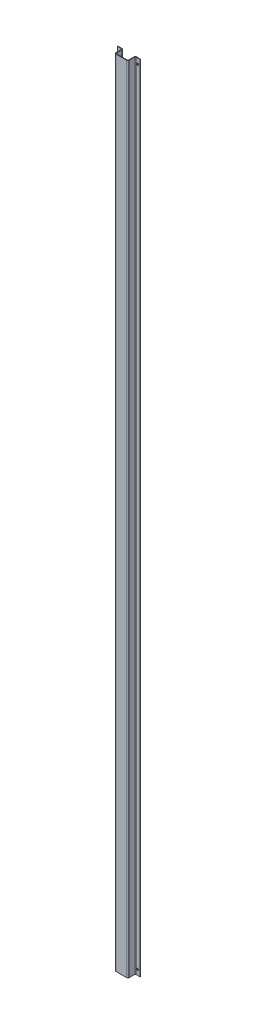
SolidWorks part; units mm, degrees
note: The reader was unsure of these and kept them because the rebuilt part matched: flange length of "Edge-Flange1", "Edge-Flange2".
material "Galvanized Steel"
ref_plane "Front" through (0, 0, 0) normal (0, 0, 1) x (1, 0, 0)
ref_plane "Top" through (0, 0, 0) normal (0, 1, 0) x (1, 0, 0)
ref_plane "Right" through (0, 0, 0) normal (1, 0, 0) x (0, 0, -1)
sketch "Sketch1" plane through (0, 0, 0) normal (0, 0, 1) x (1, 0, 0)
  line L1 (-25, -1500) -> (25, -1500)
  line L2 (-25, -1500) -> (-25, 1500)
  line L3 (-25, 1500) -> (25, 1500)
  line L4 (25, -1500) -> (25, 1500)
  line L5 (-25, -1500) -> (25, 1500) construction
  line L6 (-25, 1500) -> (25, -1500) construction
  point P0 (0, 0)
  dimension "D1" = 50
  dimension "D2" = 3000
base flange "Base-Flange1" sketch "Sketch1" thickness 2 reverse thickness direction no parameters "D1"=13
edge flange "Edge-Flange1" sketch "Sketch10" flange profiles "Sketch10", "Sketch11" flange angle 90 flange length 30 flange position material inside bend radius 2.5 thickness 2 relief rectangular parameters "D6"=10, "D8"=1
sketch "Sketch10" plane through (25, 0, -2) normal (-1, 0, 0) x (0, 1, 0)
  line L2 (-1500, 0) -> (-1500, 28)
  line L3 (-1500, 28) -> (1500, 28)
  line L4 (1500, 28) -> (1500, 0)
  line L5 (1500, 0) -> (-1500, 0) construction
  line L6 (1500, 0) -> (-1500, 0)
sketch "Sketch11" plane through (-25, 0, -2) normal (1, 0, 0) x (0, -1, 0)
  line L2 (-1500, 0) -> (-1500, 28)
  line L3 (-1500, 28) -> (1500, 28)
  line L4 (1500, 28) -> (1500, 0)
  line L5 (1500, 0) -> (-1500, 0) construction
  line L6 (1500, 0) -> (-1500, 0)
bend "EdgeBend1" bend radius 2.5 bend angle 90 parameters "D5"=1
bend "EdgeBend2" bend radius 2.5 bend angle 90 parameters "D5"=2
edge flange "Edge-Flange2" sketch "Sketch16" flange profiles "Sketch16", "Sketch17" flange angle 90 flange length 20 flange position material inside bend radius 2.5 thickness 2 relief rectangular parameters "D6"=10, "D8"=1
sketch "Sketch16" plane through (-25, 0, -30) normal (0, 0, -1) x (0, -1, 0)
  line L0 (1500, 0) -> (-1500, 0) construction
  line L1 (1500, 0) -> (-1500, 0)
  line L2 (-1500, 0) -> (-1500, 18)
  line L3 (-1500, 18) -> (1500, 18)
  line L4 (1500, 18) -> (1500, 0)
sketch "Sketch17" plane through (25, 0, -30) normal (0, 0, -1) x (0, 1, 0)
  line L0 (1500, 0) -> (-1500, 0) construction
  line L1 (1500, 0) -> (-1500, 0)
  line L2 (-1500, 0) -> (-1500, 18)
  line L3 (-1500, 18) -> (1500, 18)
  line L4 (1500, 18) -> (1500, 0)
bend "EdgeBend3" bend radius 2.5 bend angle 90 parameters "D5"=3
bend "EdgeBend4" bend radius 2.5 bend angle 90 parameters "D5"=4
sketch "Sketch18" plane through (0, 0, -28) normal (0, 0, 1) x (1, 0, 0)
  line L0 (-27.5, -1500) -> (-43, -1500) construction
  line L1 (-43, -1500) -> (-43, 1500) construction
  circle A0 centre (-34, -1480) radius 3.5
  dimension "D2" = 7
  dimension "D1" = 20
  dimension "D3" = 9
extrude "Cut-Extrude1" cut sketch "Sketch18" against normal blind 10 normal cut yes
mirror "Mirror1" about plane through (0, 0, 0) normal (0, 1, 0) of "Cut-Extrude1"
mirror "Mirror2" about plane through (0, 0, 0) normal (1, 0, 0) of "Mirror1", "Cut-Extrude1"
sketch "Bend-Lines1" [suppressed] plane through (0, 0, 0) normal (0, 1, 0) x (1, 0, 0)
sketch "Bounding-Box1" [suppressed] plane through (0, 0, 0) normal (0, 1, 0) x (1, 0, 0)
sheet metal parameters "Sheet-Metal1" thickness 2 parameters "D1"=13
flat pattern "Flat-Pattern1" [suppressed]
sketch "Bend-Lines2" plane through (0, 0, 0) normal (0, 1, 0) x (1, 0, 0)
sketch3d "Bounding-Box2" [suppressed]
  line L0 (-20, 1500, 0) -> (-20, -1500, 0) construction
  line L1 (20, 1500, 0) -> (20, -1500, 0) construction
  line L2 (-20, 1500, 0) -> (20, 1500, 0) construction
  line L3 (-20, -1500, 0) -> (20, -1500, 0) construction
sheet metal parameters "Sheet-Metal2" thickness 2 parameters "D1"=13
flat pattern "Flat-Pattern1"
sketch "Bend-Lines2" plane through (0, 0, 0) normal (0, 0, 1) x (1, 0, 0)
  line L0 (-18.2489, 1500) -> (-18.2489, -1500) construction
  line L1 (18.2489, -1500) -> (18.2489, 1500) construction
  line L2 (-18.2489, 1500) -> (-18.2489, -1500) construction
  line L3 (18.2489, -1500) -> (18.2489, 1500) construction
sketch3d "Bounding-Box2" [suppressed]
  line L0 (46.4978, 1500, 0) -> (46.4978, -1500, 0) construction
  line L1 (-46.4978, 1500, 0) -> (-46.4978, -1500, 0) construction
  line L2 (46.4978, 1500, 0) -> (-46.4978, 1500, 0) construction
  line L3 (46.4978, -1500, 0) -> (-46.4978, -1500, 0) construction
bend of the flat pattern "Flatten-<EdgeBend1>1"
bend of the flat pattern "Flatten-<EdgeBend2>1"
sheet metal parameters "Sheet-Metal3" thickness 2 parameters "D1"=13
flat pattern "Flat-Pattern1"
sketch "Bend-Lines2" plane through (0, 0, 0) normal (0, 0, 1) x (1, 0, 0)
  line L0 (-23.2489, 1500) -> (-23.2489, -1500) construction
  line L1 (23.2489, -1500) -> (23.2489, 1500) construction
  line L2 (-23.2489, 1500) -> (-23.2489, -1500) construction
  line L3 (23.2489, -1500) -> (23.2489, 1500) construction
  line L4 (49.7467, -1500) -> (49.7467, 1500) construction
  line L5 (-49.7467, 1500) -> (-49.7467, -1500) construction
  line L6 (49.7467, -1500) -> (49.7467, 1500) construction
  line L7 (-49.7467, 1500) -> (-49.7467, -1500) construction
sketch3d "Bounding-Box2" [suppressed]
  line L0 (67.9956, 1500, 0) -> (67.9956, -1500, 0) construction
  line L1 (-67.9956, 1500, 0) -> (-67.9956, -1500, 0) construction
  line L2 (67.9956, 1500, 0) -> (-67.9956, 1500, 0) construction
  line L3 (67.9956, -1500, 0) -> (-67.9956, -1500, 0) construction
bend of the flat pattern "Flatten-<EdgeBend1>1"
bend of the flat pattern "Flatten-<EdgeBend2>1"
bend of the flat pattern "Flatten-<EdgeBend3>1"
bend of the flat pattern "Flatten-<EdgeBend4>1"
sheet metal parameters "Sheet-Metal4" thickness 2 parameters "D1"=13
flat pattern "Flat-Pattern1"
sketch "Bend-Lines2" plane through (0, 0, 0) normal (0, 0, 1) x (1, 0, 0)
  line L0 (-23.2489, 1500) -> (-23.2489, -1500) construction
  line L1 (23.2489, -1500) -> (23.2489, 1500) construction
  line L2 (-23.2489, 1500) -> (-23.2489, -1500) construction
  line L3 (23.2489, -1500) -> (23.2489, 1500) construction
  line L4 (49.7467, -1500) -> (49.7467, 1500) construction
  line L5 (-49.7467, 1500) -> (-49.7467, -1500) construction
  line L6 (49.7467, -1500) -> (49.7467, 1500) construction
  line L7 (-49.7467, 1500) -> (-49.7467, -1500) construction
sketch3d "Bounding-Box2" [suppressed]
  line L0 (67.9956, 1500, 0) -> (67.9956, -1500, 0) construction
  line L1 (-67.9956, 1500, 0) -> (-67.9956, -1500, 0) construction
  line L2 (67.9956, 1500, 0) -> (-67.9956, 1500, 0) construction
  line L3 (67.9956, -1500, 0) -> (-67.9956, -1500, 0) construction
bend of the flat pattern "Flatten-<EdgeBend1>1"
bend of the flat pattern "Flatten-<EdgeBend2>1"
bend of the flat pattern "Flatten-<EdgeBend3>1"
bend of the flat pattern "Flatten-<EdgeBend4>1"
sheet metal parameters "Sheet-Metal5" thickness 2 parameters "D1"=13
flat pattern "Flat-Pattern1"
sketch "Bend-Lines2" plane through (0, 0, 0) normal (0, 0, 1) x (1, 0, 0)
  line L0 (-23.2489, 1500) -> (-23.2489, -1500) construction
  line L1 (23.2489, -1500) -> (23.2489, 1500) construction
  line L2 (-23.2489, 1500) -> (-23.2489, -1500) construction
  line L3 (23.2489, -1500) -> (23.2489, 1500) construction
  line L4 (49.7467, -1500) -> (49.7467, 1500) construction
  line L5 (-49.7467, 1500) -> (-49.7467, -1500) construction
  line L6 (49.7467, -1500) -> (49.7467, 1500) construction
  line L7 (-49.7467, 1500) -> (-49.7467, -1500) construction
sketch3d "Bounding-Box2" [suppressed]
  line L0 (67.9956, 1500, 0) -> (67.9956, -1500, 0) construction
  line L1 (-67.9956, 1500, 0) -> (-67.9956, -1500, 0) construction
  line L2 (67.9956, 1500, 0) -> (-67.9956, 1500, 0) construction
  line L3 (67.9956, -1500, 0) -> (-67.9956, -1500, 0) construction
bend of the flat pattern "Flatten-<EdgeBend1>1"
bend of the flat pattern "Flatten-<EdgeBend2>1"
bend of the flat pattern "Flatten-<EdgeBend3>1"
bend of the flat pattern "Flatten-<EdgeBend4>1"
sheet metal parameters "Sheet-Metal6" thickness 2 parameters "D1"=13
flat pattern "Flat-Pattern1"
sketch "Bend-Lines2" plane through (0, 0, 0) normal (0, 0, 1) x (1, 0, 0)
  line L0 (-23.2489, 1500) -> (-23.2489, -1500) construction
  line L1 (23.2489, -1500) -> (23.2489, 1500) construction
  line L2 (-23.2489, 1500) -> (-23.2489, -1500) construction
  line L3 (23.2489, -1500) -> (23.2489, 1500) construction
  line L4 (49.7467, -1500) -> (49.7467, 1500) construction
  line L5 (-49.7467, 1500) -> (-49.7467, -1500) construction
  line L6 (49.7467, -1500) -> (49.7467, 1500) construction
  line L7 (-49.7467, 1500) -> (-49.7467, -1500) construction
sketch3d "Bounding-Box2" [suppressed]
  line L0 (67.9956, 1500, 0) -> (67.9956, -1500, 0) construction
  line L1 (-67.9956, 1500, 0) -> (-67.9956, -1500, 0) construction
  line L2 (67.9956, 1500, 0) -> (-67.9956, 1500, 0) construction
  line L3 (67.9956, -1500, 0) -> (-67.9956, -1500, 0) construction
bend of the flat pattern "Flatten-<EdgeBend1>1"
bend of the flat pattern "Flatten-<EdgeBend2>1"
bend of the flat pattern "Flatten-<EdgeBend3>1"
bend of the flat pattern "Flatten-<EdgeBend4>1"
